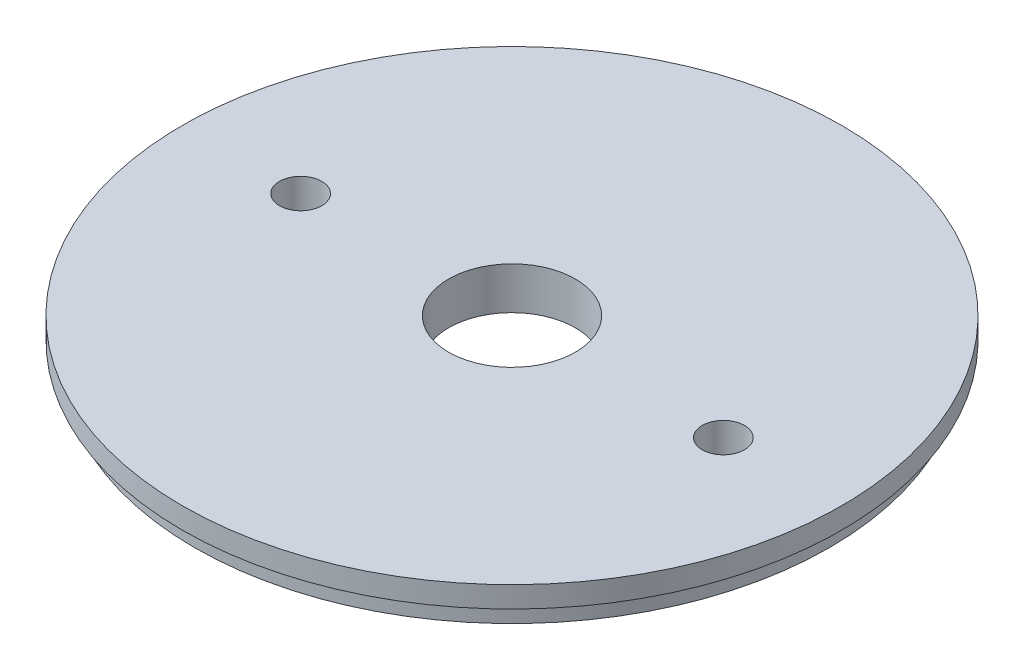
SolidWorks part; units mm, degrees
ref_plane "Front Plane" through (0, 0, 0) normal (0, 0, 1) x (1, 0, 0)
ref_plane "Top Plane" through (0, 0, 0) normal (0, 1, 0) x (1, 0, 0)
ref_plane "Right Plane" through (0, 0, 0) normal (1, 0, 0) x (0, 0, -1)
sketch "Sketch1" plane through (0, 0, 0) normal (0, 1, 0) x (1, 0, 0)
  circle A0 centre (0, 0) radius 47.6885
  dimension "D1" = 95.377
extrude "Boss-Extrude1" add sketch "Sketch1" along normal blind 3.175
sketch "Sketch2" plane through (0, 3.175, 0) normal (0, 1, 0) x (1, 0, 0)
  circle A0 centre (0, 0) radius 49.5046
  dimension "D1" = 99.0092
extrude "Boss-Extrude2" add sketch "Sketch2" along normal blind 3.175
sketch "Sketch3" plane through (0, 6.35, 0) normal (0, 1, 0) x (1, 0, 0)
  circle A0 centre (-31.75, 0) radius 3.175
  circle A1 centre (31.75, 0) radius 3.175
  circle A2 centre (0, 0) radius 9.525
  point P7 (0, 0)
  dimension "D1" = 6.35
  dimension "D2" = 6.35
  dimension "D3" = 19.05
  dimension "D4" = 63.5
  dimension "D5" = 31.75
extrude "Cut-Extrude1" cut sketch "Sketch3" against normal through all
